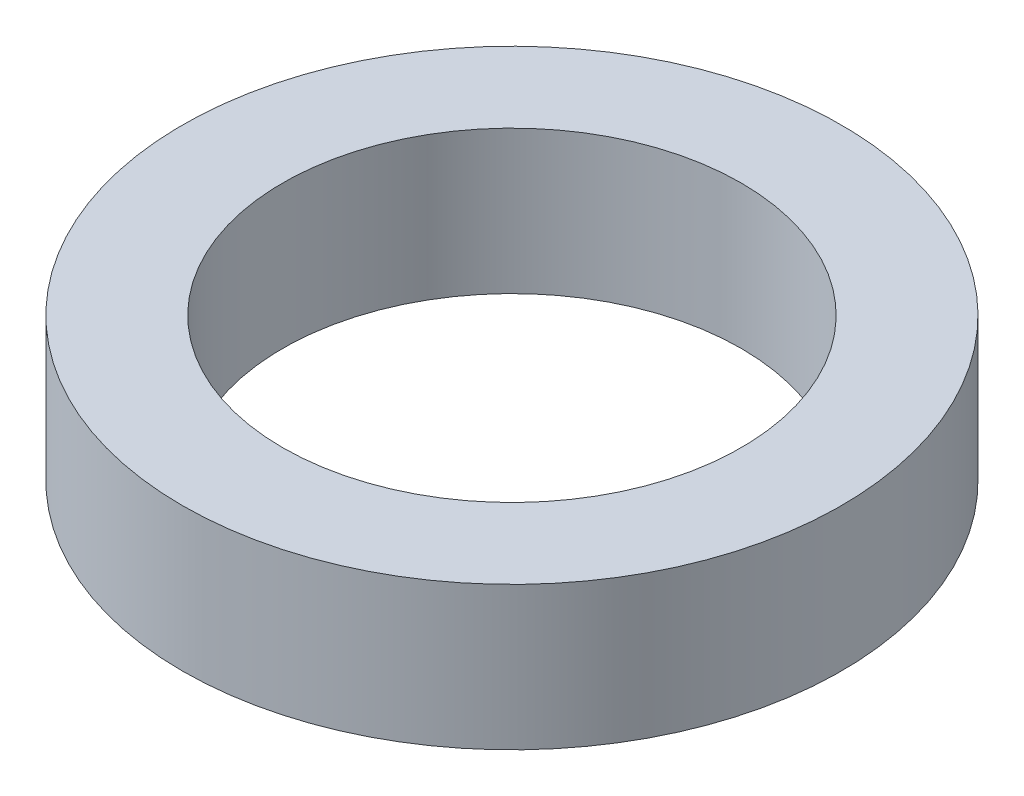
SolidWorks part; units mm, degrees
ref_plane "Front Plane" through (0, 0, 0) normal (0, 0, 1) x (1, 0, 0)
ref_plane "Top Plane" through (0, 0, 0) normal (0, 1, 0) x (1, 0, 0)
ref_plane "Right Plane" through (0, 0, 0) normal (1, 0, 0) x (0, 0, -1)
sketch "Sketch1" plane through (0, 0, 0) normal (0, 1, 0) x (1, 0, 0)
  circle A0 centre (0, 0) radius 57.5
  dimension "FLANGE_OD" = 115
extrude "Boss-Extrude1" add sketch "Sketch1" along normal blind 25
sketch "Sketch2" plane through (0, 0, 0) normal (0, 1, 0) x (1, 0, 0)
  circle A0 centre (0, 0) radius 40
  dimension "BORE_D" = 80
extrude "Cut-Extrude1" cut sketch "Sketch2" along normal through all
sketch "Sketch3" plane through (0, 25, 0) normal (0, 1, 0) x (1, 0, 0)
  circle A0 centre (0, 0) radius 25.7815 construction
  circle A1 centre (-25.7815, 0) radius 2.3071
  dimension "BOLT_D" = 4.6141
  dimension "BOLT_PCD" = 51.5629
extrude "Cut-Extrude2" cut sketch "Sketch3" against normal blind 15.7676 rebuild error yes
pattern_circular "CirPattern1" count 3 over 360 rebuild error yes
